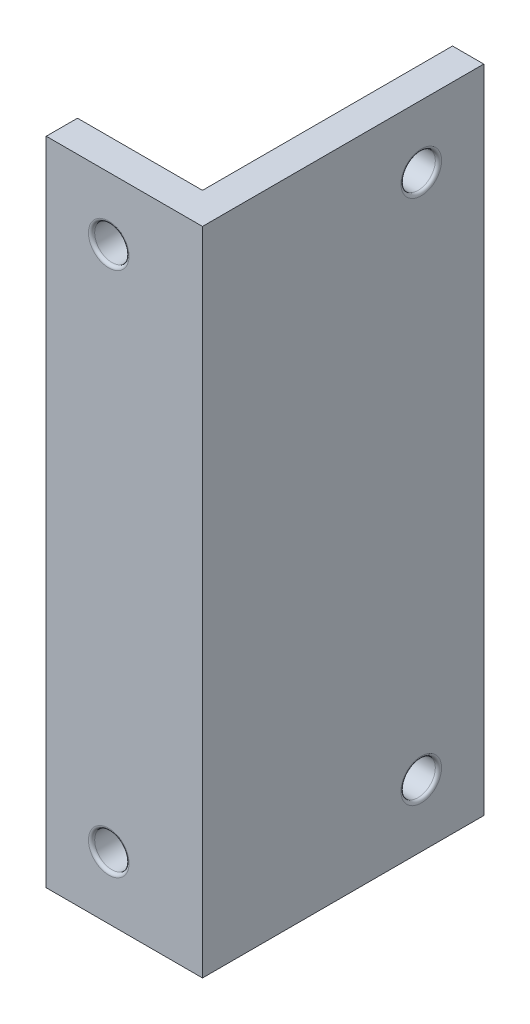
SolidWorks part; units mm, degrees
ref_plane "Front Plane" through (0, 0, 0) normal (0, 0, 1) x (1, 0, 0)
ref_plane "Top Plane" through (0, 0, 0) normal (0, 1, 0) x (1, 0, 0)
ref_plane "Right Plane" through (0, 0, 0) normal (1, 0, 0) x (0, 0, -1)
sketch "Sketch1" plane through (0, 0, 0) normal (0, 1, 0) x (1, 0, 0)
  line L0 (7.5, 2.5) -> (12.5, 2.5) construction
  line L1 (-12.5, -2.5) -> (12.5, -2.5)
  line L2 (-12.5, -2.5) -> (-12.5, 2.5)
  line L3 (-12.5, 2.5) -> (7.5, 2.5)
  line L4 (12.5, -2.5) -> (12.5, 2.5)
  line L6 (-12.5, 2.5) -> (12.5, -2.5) construction
  line L8 (12.5, 2.5) -> (12.5, 42.5)
  line L9 (12.5, 42.5) -> (7.5, 42.5)
  line L10 (7.5, 2.5) -> (7.5, 42.5)
  point P0 (0, 0)
  point P9 (0, 0)
  dimension "D1" = 20
  dimension "D2" = 5
  dimension "D3" = 5
  dimension "D4" = 40
extrude "Boss-Extrude1" add sketch "Sketch1" along normal blind 104.14
sketch "Sketch2" plane through (0, 0, 2.5) normal (0, 0, 1) x (1, 0, 0)
  line L0 (7.5, 94.14) -> (-12.5, 94.14) construction
  line L2 (-12.5, 104.14) -> (-12.5, 0) construction
  line L3 (12.5, 104.14) -> (12.5, 0) construction
  line L4 (-12.5, 104.14) -> (12.5, 104.14) construction
  line L5 (12.5, 52.07) -> (-12.5, 52.07) construction
  circle A0 centre (-2.5, 94.14) radius 2.75
  circle A2 centre (-2.5, 10) radius 2.75
  dimension "D3" = 5.5
  dimension "D1" = 5
  dimension "D2" = 10
extrude "Cut-Extrude1" cut sketch "Sketch2" against normal through all
sketch "Sketch3" plane through (12.5, 0, 0) normal (1, 0, 0) x (0, 0, -1)
  line L0 (-2.5, 104.14) -> (42.5, 104.14) construction
  line L8 (2.5, 104.14) -> (2.5, 0) construction
  line L9 (2.5, 104.14) -> (2.5, 0) construction
  line L10 (2.5, 52.07) -> (42.5, 52.07) construction
  line L11 (42.5, 104.14) -> (42.5, 0) construction
  circle A0 centre (32.5, 94.14) radius 2.75
  circle A1 centre (32.5, 10) radius 2.75
  dimension "D1" = 5.5
  dimension "D2" = 10
  dimension "D3" = 30
extrude "Cut-Extrude2" cut sketch "Sketch3" against normal through all
fillet "Fillet1" radius 0.5 8 edges at (7.5, 94.14, -35.25) (12.5, 94.14, -35.25) (7.5, 10, -35.25) (12.5, 10, -29.75) (0.25, 10, -2.5) (-5.25, 10, 2.5) (0.25, 94.14, -2.5) (0.25, 94.14, 2.5)
